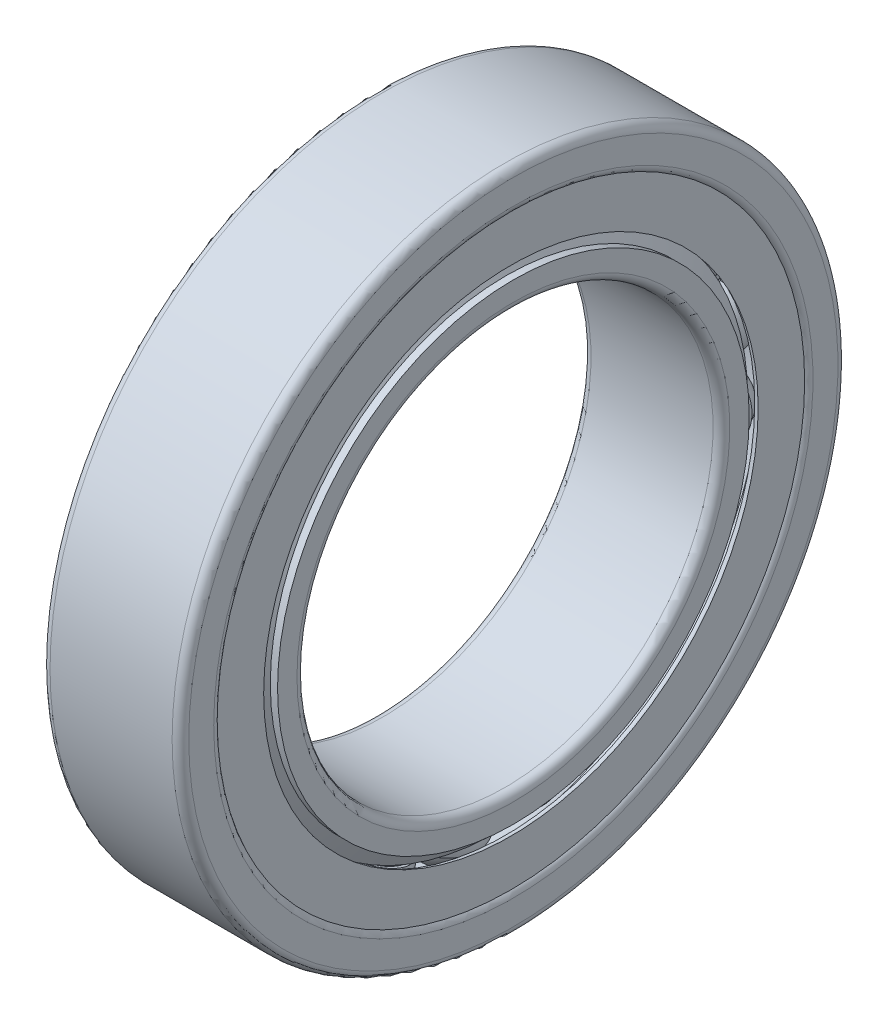
SolidWorks part; units mm, degrees
ref_plane "前视基准面" through (0, 0, 0) normal (0, 0, 1) x (1, 0, 0)
ref_plane "上视基准面" through (0, 0, 0) normal (0, 1, 0) x (1, 0, 0)
ref_plane "右视基准面" through (0, 0, 0) normal (1, 0, 0) x (0, 0, -1)
sketch "尺寸草图" plane through (0, 0, 0) normal (0, 0, 1) x (1, 0, 0)
  line L0 (-19.9271, 0) -> (19.9271, 0) construction
  line L1 (0, 21.603) -> (0, -21.603) construction
  line L2 (-2.2, 12) -> (2.2, 12)
  line L3 (2.5, 11.7) -> (2.5, 10.8)
  line L4 (-2.5, 11.7) -> (-2.5, 10.8)
  line L5 (-2.2, 10.5) -> (2.2, 10.5)
  line L6 (-3.5, 9.75) -> (3.3577, 9.75) construction
  line L7 (-2.2, 9) -> (2.2, 9)
  line L8 (2.5, 8.7) -> (2.5, 7.8)
  line L9 (2.2, 7.5) -> (-2.2, 7.5)
  line L10 (-2.5, 7.8) -> (-2.5, 8.7)
  line L11 (0, 9.75) -> (0, 10.875) construction
  line L13 (2.2, 10.5) -> (2.2, 9)
  line L14 (1.95, 9) -> (2.2387, 8.5)
  line L15 (2.2387, 8.5) -> (2.5, 8.5)
  line L16 (2.4121, 10.5879) -> (2.4121, 8.9121)
  circle A0 centre (0, 9.75) radius 1.125
  arc A1 (2.5, 10.8) -> (2.2, 10.5) centre (2.2, 10.8) cw
  arc A2 (2.5, 8.7) -> (2.2, 9) centre (2.2, 8.7) ccw
  arc A3 (-2.2, 9) -> (-2.5, 8.7) centre (-2.2, 8.7) ccw
  arc A4 (-2.2, 10.5) -> (-2.5, 10.8) centre (-2.2, 10.8) cw
  arc A5 (-2.2, 7.5) -> (-2.5, 7.8) centre (-2.2, 7.8) cw
  arc A6 (2.2, 7.5) -> (2.5, 7.8) centre (2.2, 7.8) ccw
  arc A7 (2.5, 11.7) -> (2.2, 12) centre (2.2, 11.7) ccw
  arc A8 (-2.2, 12) -> (-2.5, 11.7) centre (-2.2, 11.7) ccw
  point P7 (0, 0)
  point P25 (-2.5, 9)
  point P28 (-2.5, 10.5)
  point P31 (-2.5, 7.5)
  point P36 (2.5, 12)
  point P39 (-2.5, 12)
  dimension "D1" = 0.375
  dimension "D3" = 0.3
  dimension "B" = 5
  dimension "D2" = 2.5
  dimension "D" = 24
  dimension "(d)" = 15
  dimension "D5" = 9.75
  dimension "D6" = 1.5
  dimension "D7" = 1.5
  dimension "D8" = 0.5
  dimension "D9" = 60
  dimension "D10" = 0.55
sketch "草图2" plane through (0, 0, 0) normal (0, 0, 1) x (1, 0, 0)
  line L0 (1.95, 9) -> (2.2387, 8.5) construction
  line L1 (2.2387, 8.5) -> (2.5, 8.5) construction
  line L2 (1.95, 9) -> (2.2387, 8.5)
  line L3 (2.2387, 8.5) -> (2.5, 8.5)
  line L4 (0, 10.875) -> (0, 8.625) construction
  line L5 (-2.2387, 8.5) -> (-2.5, 8.5)
  line L6 (2.2, 7.5) -> (-2.2, 7.5) construction
  line L7 (-1.95, 9) -> (-2.2387, 8.5)
  line L8 (-2.5, 11.7) -> (-2.5, 10.8) construction
  line L9 (-2.2, 10.5) -> (2.2, 10.5) construction
  line L10 (-2.2, 12) -> (2.2, 12) construction
  line L11 (2.5, 11.7) -> (2.5, 10.8) construction
  line L12 (2.5, 8.7) -> (2.5, 7.8) construction
  line L13 (-2.2, 9) -> (2.2, 9) construction
  line L14 (2.2, 7.5) -> (-2.2, 7.5)
  line L15 (-2.5, 7.8) -> (-2.5, 8.7) construction
  line L18 (-3.5, 0) -> (3.5, 0) construction
  line L19 (-19.9271, 0) -> (19.9271, 0) construction
  line L20 (-2.5, 11.7) -> (-2.5, 10.8)
  line L21 (-2.2, 10.5) -> (-0.8385, 10.5)
  line L22 (-2.2, 12) -> (2.2, 12)
  line L23 (2.5, 11.7) -> (2.5, 10.8)
  line L24 (2.5, 8.5) -> (2.5, 7.8)
  line L25 (-1.95, 9) -> (-0.8385, 9)
  line L26 (-2.5, 7.8) -> (-2.5, 8.5)
  line L27 (0.8385, 10.5) -> (2.2, 10.5)
  line L28 (0.8385, 9) -> (1.95, 9)
  circle A0 centre (0, 9.75) radius 1.125 construction
  arc A1 (0.8385, 10.5) -> (-0.8385, 10.5) centre (0, 9.75) ccw
  arc A2 (-0.8385, 9) -> (0.8385, 9) centre (0, 9.75) ccw
  arc A3 (-2.2, 12) -> (-2.5, 11.7) centre (-2.2, 11.7) ccw construction
  arc A4 (-2.5, 10.8) -> (-2.2, 10.5) centre (-2.2, 10.8) ccw construction
  arc A5 (2.5, 11.7) -> (2.2, 12) centre (2.2, 11.7) ccw construction
  arc A6 (2.2, 10.5) -> (2.5, 10.8) centre (2.2, 10.8) ccw construction
  arc A8 (2.2, 7.5) -> (2.5, 7.8) centre (2.2, 7.8) ccw construction
  arc A10 (-2.5, 7.8) -> (-2.2, 7.5) centre (-2.2, 7.8) ccw construction
  arc A11 (-2.2, 12) -> (-2.5, 11.7) centre (-2.2, 11.7) ccw
  arc A12 (-2.5, 10.8) -> (-2.2, 10.5) centre (-2.2, 10.8) ccw
  arc A13 (2.5, 11.7) -> (2.2, 12) centre (2.2, 11.7) ccw
  arc A14 (2.2, 10.5) -> (2.5, 10.8) centre (2.2, 10.8) ccw
  arc A16 (2.2, 7.5) -> (2.5, 7.8) centre (2.2, 7.8) ccw
  arc A18 (-2.5, 7.8) -> (-2.2, 7.5) centre (-2.2, 7.8) ccw
revolve "旋转1" add sketch "草图2" angle 360 about L18
sketch "草图5" plane through (0, 0, 0) normal (0, 0, 1) x (1, 0, 0)
  line L1 (-0.3375, 9.525) -> (0.3375, 9.525)
  line L2 (-0.3375, 9.525) -> (-0.3375, 9.975)
  line L3 (-0.3375, 9.975) -> (0.3375, 9.975)
  line L4 (0.3375, 9.525) -> (0.3375, 9.975)
  line L5 (-0.3375, 9.525) -> (0.3375, 9.975) construction
  line L6 (-0.3375, 9.975) -> (0.3375, 9.525) construction
  circle A0 centre (0, 9.75) radius 1.125 construction
  circle A1 centre (0, 9.75) radius 1.125 construction
  point P0 (0, 9.75)
  dimension "D3" = 2.25
  dimension "D1" = 0.675
  dimension "D2" = 0.45
revolve "旋转3" add sketch "草图5" angle 360 about L0
sketch "草图3" plane through (0, 0, 0) normal (0, 0, 1) x (1, 0, 0)
  line L1 (-1.2375, 9.75) -> (1.2375, 9.75)
  circle A0 centre (0, 9.75) radius 1.125 construction
  circle A1 centre (0, 9.75) radius 1.125 construction
  arc A2 (1.2375, 9.75) -> (-1.2375, 9.75) centre (0, 9.75) ccw
  dimension "D2" = 2.475
revolve "旋转2" add sketch "草图3" angle 360 about L1 region at (0, 10.2752, 0)
ref_axis "基准轴1" through (-3.85, 0, 0) along (1, 0, 0)
pattern_circular "阵列(圆周)5" count 22 over 360 about axis through (-3.85, 0, 0) along (1, 0, 0) of bodies 103
sketch "草图6" plane through (0, 0, 0) normal (0, 0, 1) x (1, 0, 0)
  line L0 (-1.2169, 9.975) -> (1.2169, 9.975)
  line L1 (-3.5, 9.75) -> (2.5, 9.75) construction
  line L3 (-1.2169, 9.525) -> (1.2169, 9.525)
  line L4 (2.5, -11.7) -> (2.5, 11.7) construction
  arc A0 (-1.2169, 9.525) -> (1.2169, 9.525) centre (0, 9.75) ccw
  circle A1 centre (0, 9.75) radius 1.125 construction
  circle A2 centre (0, 9.75) radius 1.125 construction
  arc A3 (1.2169, 9.975) -> (-1.2169, 9.975) centre (0, 9.75) ccw
  dimension "D1" = 2.475
  dimension "D2" = 2.25
  dimension "D3" = 0.225
  dimension "D4" = 0.225
revolve "切除-旋转1" cut sketch "草图6" angle 360 about L0
sketch "草图7" plane through (0, 0, 0) normal (0, 0, 1) x (1, 0, 0)
  line L0 (-1.125, 9.75) -> (1.125, 9.75)
  line L1 (-2.5, 0) -> (2.4587, 0) construction
  line L2 (-2.5, 11.7) -> (-2.5, -11.7) construction
  line L3 (-19.9271, 0) -> (19.9271, 0) construction
  circle A0 centre (0, 9.75) radius 1.125 construction
  arc A1 (1.125, 9.75) -> (-1.125, 9.75) centre (0, 9.75) ccw
revolve "旋转4" add sketch "草图7" angle 360 about L0
pattern_circular "阵列(圆周)2" count 22 over 360 about axis through (-3.85, 0, 0) along (1, 0, 0) of "旋转4" reverse direction yes
sketch "草图9" plane through (0, 0, 0) normal (0, 0, 1) x (1, 0, 0)
  line L1 (2.2, 10.5) -> (2.2, 9) construction
  line L4 (2.4121, 10.5879) -> (2.4121, 8.9121) construction
  line L5 (2.2, 10.5) -> (2.2, 9)
  line L6 (2.4121, 10.5879) -> (2.4121, 8.9121)
  line L7 (-2.4121, 10.5879) -> (-2.4121, 8.9121)
  line L8 (0, 12) -> (0, 0) construction
  line L9 (-2.2, 12) -> (2.2, 12) construction
  line L10 (-2.2, 10.5) -> (-2.2, 9)
  arc A0 (2.2, 10.5) -> (2.5, 10.8) centre (2.2, 10.8) ccw construction
  arc A1 (2.2, 10.5) -> (2.4121, 10.5879) centre (2.2, 10.8) ccw
  arc A2 (2.5, 8.7) -> (2.2, 9) centre (2.2, 8.7) ccw construction
  arc A3 (2.4121, 8.9121) -> (2.2, 9) centre (2.2, 8.7) ccw
  arc A4 (-2.4121, 8.9121) -> (-2.2, 9) centre (-2.2, 8.7) cw
  arc A5 (-2.2, 10.5) -> (-2.4121, 10.5879) centre (-2.2, 10.8) cw
revolve "旋转5" add sketch "草图9" angle 360 about L0
